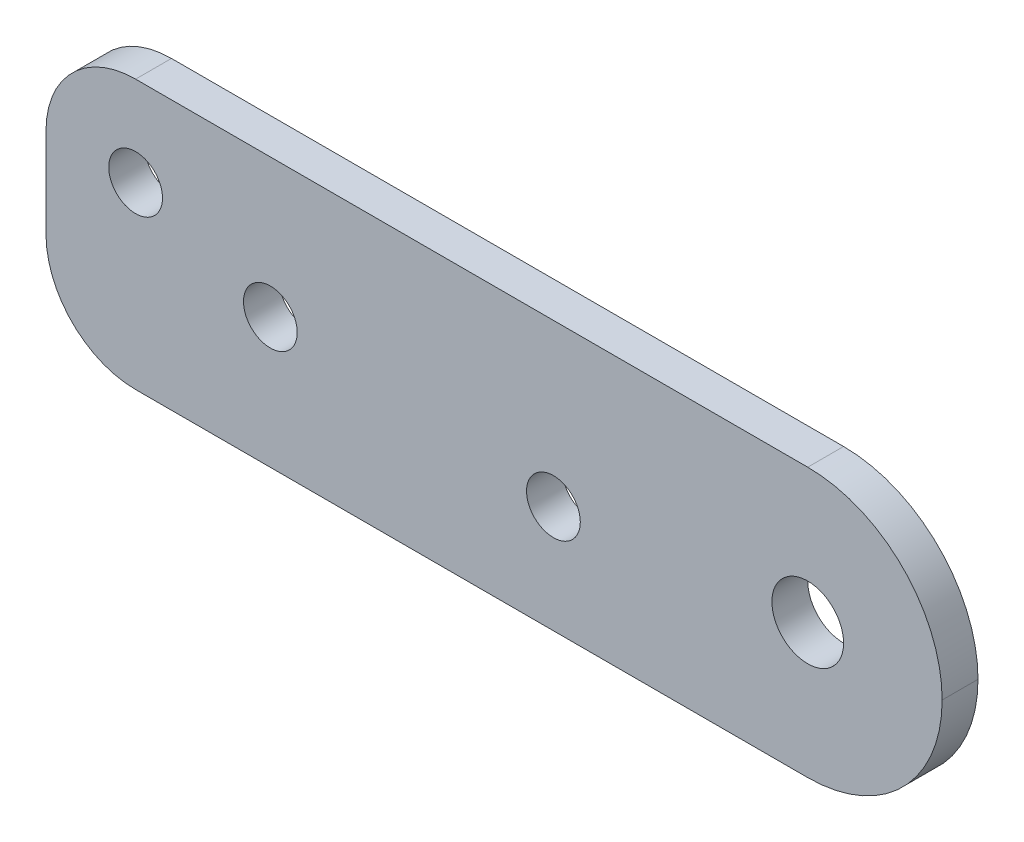
SolidWorks part; units mm, degrees
material "Thornel Mat VMA"
ref_plane "前视基准面" through (0, 0, 0) normal (0, 0, 1) x (1, 0, 0)
ref_plane "上视基准面" through (0, 0, 0) normal (0, 1, 0) x (1, 0, 0)
ref_plane "右视基准面" through (0, 0, 0) normal (1, 0, 0) x (0, 0, -1)
sketch "草图1" plane through (0, 0, 0) normal (0, 0, 1) x (1, 0, 0)
  line L1 (-25, -7.5) -> (25, -7.5)
  line L2 (-25, -7.5) -> (-25, 7.5)
  line L3 (-25, 7.5) -> (25, 7.5)
  line L4 (25, -7.5) -> (25, 7.5)
  line L5 (-25, -7.5) -> (25, 7.5) construction
  line L6 (-25, 7.5) -> (25, -7.5) construction
  point P0 (0, 0)
  dimension "D1" = 50
  dimension "D2" = 15
extrude "凸台-拉伸1" add sketch "草图1" along normal blind 2
fillet "圆角1" radius 5 2 edges at (-25, -7.5, 1) (-25, 7.5, 1)
fillet "圆角2" radius 7.5 2 edges at (25, -7.5, 1) (25, 7.5, 1)
sketch "草图3" plane through (0, 0, 2) normal (0, 0, 1) x (1, 0, 0)
  line L1 (-20, 2.5) -> (-20, -12.0218) construction
  line L2 (25, 0) -> (24.851, 0) construction
  line L3 (17.5, 7.5) -> (17.5, -2.3276) construction
  line L4 (-20, 2.5) -> (-12.4825, -0.2362) construction
  circle A0 centre (-20, 2.5) radius 1.5
  circle A1 centre (-12.4825, -0.2362) radius 1.5
  circle A2 centre (17.5, 0) radius 2
  dimension "D1" = 3
  dimension "D3" = 70
  dimension "D4" = 4
  dimension "D2" = 8
extrude "切除-拉伸1" cut sketch "草图3" against normal blind 2
sketch "草图4" plane through (0, 0, 2) normal (0, 0, 1) x (1, 0, 0)
  circle A0 centre (3.3106, -1.5) radius 1.5 construction
  circle A1 centre (3.3106, -1.5) radius 1.5
extrude "切除-拉伸2" cut sketch "草图4" against normal blind 10 contours A1
